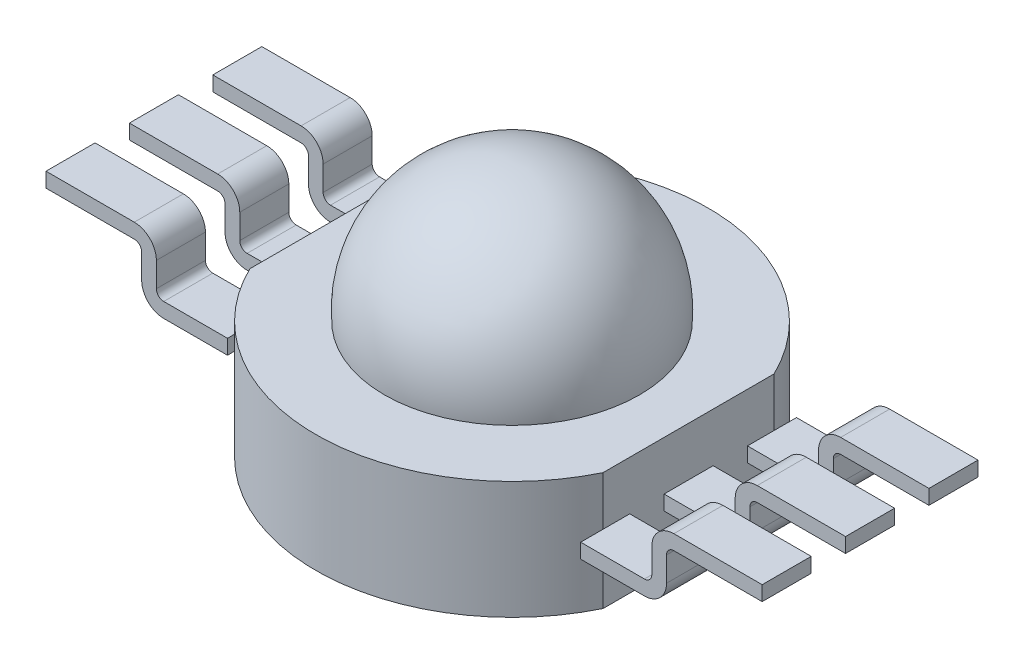
SolidWorks part; units mm, degrees
material "ABS"
ref_plane "Front Plane" through (0, 0, 0) normal (0, 0, 1) x (1, 0, 0)
ref_plane "Top Plane" through (0, 0, 0) normal (0, 1, 0) x (1, 0, 0)
ref_plane "Right Plane" through (0, 0, 0) normal (1, 0, 0) x (0, 0, -1)
sketch "Sketch1" plane through (0, 0, 0) normal (0, 1, 0) x (1, 0, 0)
  line L0 (-3.6, 1.7436) -> (-3.6, -1.7436)
  line L1 (3.6, 1.7436) -> (3.6, -1.7436)
  arc A0 (3.6, 1.7436) -> (-3.6, 1.7436) centre (0, 0) ccw
  arc A1 (-3.6, -1.7436) -> (3.6, -1.7436) centre (0, 0) ccw
  dimension "D1" = 8
  dimension "D2" = 7.2
extrude "LED Base Boss-Extrude1" add sketch "Sketch1" along normal blind 2.4
sketch "Sketch3" plane through (0, 0, 0) normal (0, 0, 1) x (1, 0, 0)
  line L0 (0, 0) -> (0, 5.0961) construction
  line L1 (3.6, 2.4) -> (-3.6, 2.4) construction
  line L2 (0, 5.2) -> (2.6, 5.2) construction
  line L3 (2.6, 2.4) -> (2.6, 5.2) construction
  line L4 (2.6, 2.4) -> (0, 2.4)
  line L5 (0, 5.2) -> (0, 2.4)
  arc A0 (0, 5.2) -> (2.6, 2.4) centre (0, 2.5929) cw
  dimension "D1" = 2.6
  dimension "D2" = 5.2
revolve "LED Lens Revolve2" add sketch "Sketch3" angle 360 about L5
sketch "Sketch4" plane through (0, 0, 0) normal (0, 0, 1) x (1, 0, 0)
  line L0 (3.6, 2.4) -> (3.6, 0) construction
  line L1 (3.6, 1.4) -> (4.9, 1.4)
  line L2 (3.6, 1.4) -> (3.6, 1.1)
  line L3 (3.6, 1.1) -> (4.9, 1.1)
  line L4 (5.05, 0.95) -> (5.05, 0.45) construction
  line L5 (5.35, 0.95) -> (5.35, 0.45) construction
  line L6 (4.9, 1.4) -> (4.9, 1.1) construction
  line L7 (5.5, 0.3) -> (5.5, 0) construction
  line L8 (5.05, 0.7) -> (5.35, 0.7) construction
  line L9 (-3.6, 0) -> (3.6, 0) construction
  line L10 (5.5, 0) -> (7.3, 0) construction
  line L11 (5.05, 1.55) -> (5.05, 2.05)
  line L12 (5.5, 0.3) -> (7.3, 0.3) construction
  line L13 (7.3, 0) -> (7.3, 0.3) construction
  line L14 (5.35, 1.55) -> (5.35, 2.05)
  line L15 (5.5, 2.5) -> (7.3, 2.5)
  line L16 (7.3, 2.5) -> (7.3, 2.2)
  line L17 (7.3, 2.2) -> (5.5, 2.2)
  line L18 (5.35, 1.8) -> (5.05, 1.8) construction
  line L19 (5.5, 2.2) -> (5.5, 2.5) construction
  arc A0 (4.9, 1.4) -> (5.35, 0.95) centre (4.9, 0.95) cw construction
  arc A1 (4.9, 1.1) -> (5.05, 0.95) centre (4.9, 0.95) cw construction
  arc A2 (5.05, 0.45) -> (5.5, 0) centre (5.5, 0.45) ccw construction
  arc A3 (5.35, 0.45) -> (5.5, 0.3) centre (5.5, 0.45) ccw construction
  arc A4 (4.9, 1.4) -> (5.05, 1.55) centre (4.9, 1.55) ccw
  arc A5 (4.9, 1.1) -> (5.35, 1.55) centre (4.9, 1.55) ccw
  arc A6 (5.35, 2.05) -> (5.5, 2.2) centre (5.5, 2.05) cw
  arc A7 (5.05, 2.05) -> (5.5, 2.5) centre (5.5, 2.05) cw
  dimension "D1" = 3.7
  dimension "D2" = 0.3
  dimension "D3" = 1.4
  dimension "D4" = 0
  dimension "D5" = 0.5
  dimension "D6" = 1.3
  dimension "D7" = 1.8
  dimension "D8" = 1.4
  dimension "D9" = 2.2
extrude "Pin Right Boss-Extrude2" add sketch "Sketch4" along normal blind 2.2 and the other way blind 2.2
sketch "Sketch5" plane through (0, 1.4, 0) normal (0, 1, 0) x (1, 0, 0)
  line L0 (3.6, -1.7436) -> (3.6, 1.7436) construction
  line L1 (3.6, 1.2) -> (7.3, 1.2)
  line L2 (3.6, 1.2) -> (3.6, 0.5)
  line L3 (3.6, 0.5) -> (7.3, 0.5)
  line L4 (7.3, 1.2) -> (7.3, 0.5)
  line L6 (0, 0) -> (1.3969, 0) construction
  line L7 (7.3, -0.5) -> (3.6, -0.5)
  line L8 (7.3, -0.5) -> (7.3, -1.2)
  line L9 (7.3, -1.2) -> (3.6, -1.2)
  line L10 (3.6, -0.5) -> (3.6, -1.2)
  line L11 (3.6, -0.5) -> (3.6, 0) construction
  line L12 (3.6, 1.7436) -> (3.6, -1.7436) construction
  line L13 (3.6, 0) -> (3.6, 0.5) construction
  line L14 (7.3, 2.2) -> (7.3, 1.2) construction
  line L15 (7.3, 0.5) -> (7.3, -0.5) construction
  line L16 (7.3, -1.2) -> (7.3, -2.2) construction
  line L17 (7.3, 2.2) -> (5.5, 2.2) construction
  line L18 (7.3, 2.2) -> (7.3, -2.2) construction
  dimension "D1" = 0.7
  dimension "D2" = 1
  dimension "D3" = 4.4
extrude "Pin Right Space Cut-Extrude1" cut sketch "Sketch5" along normal up to surface and the other way up to surface up to face at (6.4, 2.5, 0) other way up to face at (4.0333, 1.1, 0)
mirror "Pin Left Mirror1" about plane through (0, 0, 0) normal (1, 0, 0) of "Pin Right Space Cut-Extrude1", "Pin Right Boss-Extrude2"
sketch "Sketch6" plane through (0, 0, 0) normal (0, -1, 0) x (1, 0, 0)
  circle A0 centre (0, 0) radius 2.7
  dimension "D1" = 5.4
extrude "Heatsink Boss-Extrude3" add sketch "Sketch6" along normal blind 0.1
equation "\"D1@Sketch3\"=5.2/2"
equation "\"D1@Sketch4\"=(14.60-7.2)/2"
equation "\"D1@Pin Right Boss-Extrude2\"=(1+0.7+1+0.7+1)/2"
equation "\"D2@Pin Right Boss-Extrude2\"=(1+0.7+1+0.7+1)/2"
